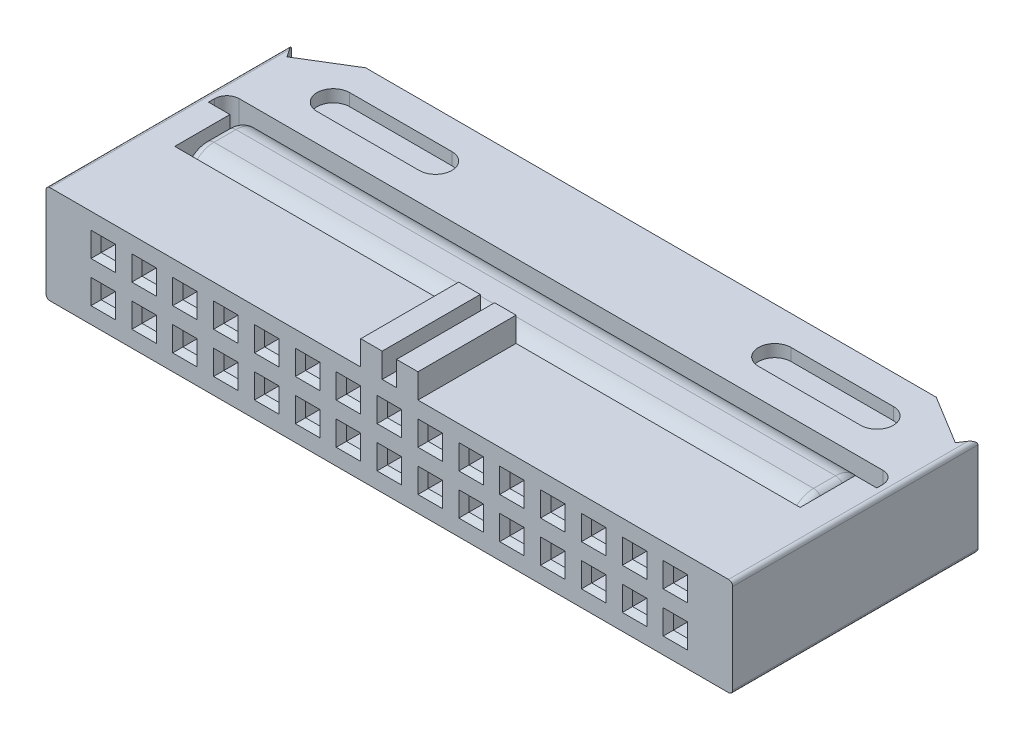
SolidWorks part; units mm, degrees
extrude "Base-Extrude" add sketch "Sketch1" against normal blind 16.256
sketch "Sketch1" plane through (0, 0, 0) normal (0, 0, 1) x (1, 0, 0)
  line L1 (-21.082, 3.048) -> (-1.778, 3.048)
  line L2 (-21.336, 2.794) -> (-21.336, -2.794)
  line L3 (-21.082, -3.048) -> (21.082, -3.048)
  line L4 (21.336, 2.794) -> (21.336, -2.794)
  line L5 (0, -6.7653) -> (0, 6.7653) construction
  line L6 (16.5234, 0) -> (-16.5234, 0) construction
  line L7 (1.778, 3.048) -> (21.082, 3.048)
  line L8 (-1.778, 4.572) -> (-0.4445, 4.572)
  line L9 (-1.778, 4.572) -> (-1.778, 3.048)
  line L10 (0.4445, 4.572) -> (1.778, 4.572)
  line L11 (1.778, 4.572) -> (1.778, 3.048)
  line L13 (-0.4445, 4.572) -> (-0.4445, 3.048)
  line L14 (-0.4445, 3.048) -> (0.4445, 3.048)
  line L15 (0.4445, 4.572) -> (0.4445, 3.048)
  arc A0 (-21.082, 3.048) -> (-21.336, 2.794) centre (-21.082, 2.794) ccw
  arc A1 (-21.336, -2.794) -> (-21.082, -3.048) centre (-21.082, -2.794) ccw
  arc A2 (21.336, -2.794) -> (21.082, -3.048) centre (21.082, -2.794) cw
  arc A3 (21.082, 3.048) -> (21.336, 2.794) centre (21.082, 2.794) cw
  point P4 (0, 3.048)
  point P7 (-21.336, 0)
  point P14 (0, 4.572)
  point P15 (0, 3.048)
  point P26 (21.336, -3.048)
  point P29 (21.336, 3.048)
  dimension "D8" = 0.254
  dimension "D9" = 0.254
  dimension "D1" = 42.672
  dimension "D2" = 6.096
  dimension "D3" = 3.556
  dimension "D4" = 1.524
  dimension "D5" = 0.889
  dimension "D6" = 1.778
  dimension "D7" = 21.336
ref_plane "Front" through (0, 0, 0) normal (0, 0, 1) x (1, 0, 0)
ref_plane "Top" through (0, 0, 0) normal (0, 1, 0) x (1, 0, 0)
ref_plane "Right" through (0, 0, 0) normal (1, 0, 0) x (0, 0, -1)
sketch "Sketch2" plane through (0, 3.048, 0) normal (0, 1, 0) x (-1, 0, 0)
  line L0 (-17.7294, -16.256) -> (-20.7645, -14.403)
  line L1 (-20.7645, -14.403) -> (-21.336, -15.2431)
  line L2 (21.336, -16.256) -> (21.336, -15.2431)
  line L3 (0, -17.4041) -> (0, 0.7826) construction
  line L4 (20.7645, -14.403) -> (21.336, -15.2431)
  line L5 (17.7294, -16.256) -> (20.7645, -14.403)
  line L6 (21.336, -16.256) -> (17.7294, -16.256)
  line L7 (-21.336, -16.256) -> (-21.336, -15.2431)
  line L8 (-21.336, -16.256) -> (-17.7294, -16.256)
  line L11 (-20.0025, -10.668) -> (20.0025, -10.668)
  line L12 (-20.7645, -9.525) -> (20.7645, -9.525)
  line L13 (-20.7645, -9.906) -> (-20.7645, -9.525)
  line L14 (20.7645, -9.906) -> (20.7645, -9.525)
  line L15 (0, 6.7653) -> (0, -6.7653) construction
  line L16 (-21.336, -16.256) -> (-21.336, 0) construction
  line L17 (-21.082, -16.256) -> (-1.778, -16.256) construction
  arc A0 (-20.7645, -9.906) -> (-20.0025, -10.668) centre (-20.0025, -9.906) ccw
  arc A1 (20.7645, -9.906) -> (20.0025, -10.668) centre (20.0025, -9.906) cw
  point P20 (0, -10.668)
  point P24 (0, -9.525)
  dimension "D1" = 0.762
  dimension "D2" = 40.005
  dimension "D3" = 5.588
  dimension "D4" = 1.143
  dimension "D5" = 3.556
  dimension "D6" = 1.016
  dimension "D7" = 1.853
extrude "Cut-Extrude1" cut sketch "Sketch2" against normal through all
sketch "Sketch3" plane through (-1.778, 0, 0) normal (-1, 0, 0) x (0, 0, 1)
  line L0 (0, -6.3682) -> (0, 6.3682) construction
  line L1 (-16.256, 4.572) -> (-6.096, 4.572)
  line L2 (-16.256, 4.572) -> (-16.256, 3.048)
  line L3 (-16.256, 3.048) -> (-6.096, 3.048)
  line L4 (-6.096, 4.572) -> (-6.096, 3.048)
  line L5 (-14.8697, 3.048) -> (0, 3.048) construction
  dimension "D1" = 6.096
extrude "Cut-Extrude2" cut sketch "Sketch3" against normal through all
sketch "Sketch4" plane through (0, 0, 0) normal (0, 0, 1) x (1, 0, 0)
  line L0 (-12.4713, 1.27) -> (21.336, 1.27) construction
  line L1 (-12.4713, -1.27) -> (21.336, -1.27) construction
  line L2 (17.78, 3.048) -> (17.78, -3.048) construction
  line L4 (21.336, -2.794) -> (21.336, 2.794) construction
  line L6 (21.336, 1.27) -> (21.336, -1.27) construction
  line L7 (16.5234, 0) -> (-16.5234, 0) construction
  line L8 (17.3355, -0.8255) -> (18.2245, -0.8255)
  line L9 (17.3355, -0.8255) -> (17.3355, -1.7145)
  line L10 (17.3355, -1.7145) -> (18.2245, -1.7145)
  line L11 (17.3355, 1.7145) -> (18.2245, 1.7145)
  line L12 (17.3355, 1.7145) -> (17.3355, 0.8255)
  line L13 (17.3355, 0.8255) -> (18.2245, 0.8255)
  line L14 (18.2245, 1.7145) -> (18.2245, 0.8255)
  line L15 (18.2245, -0.8255) -> (18.2245, -1.7145)
  point P11 (21.336, 0)
  point P16 (18.2245, -1.27)
  point P17 (17.3355, -1.27)
  point P23 (17.78, 1.7145)
  point P24 (18.2245, 1.27)
  point P25 (17.78, -1.7145)
  dimension "D1" = 3.556
  dimension "D2" = 0.889
  dimension "D3" = 2.54
  dimension "D4" = 0.889
  dimension "D6" = 0.889
  dimension "D7" = 0.889
extrude "Cut-Extrude3" cut sketch "Sketch4" against normal up to surface (6.096 mm away) up to face at (1.1113, 3.81, -6.096)
sketch "Sketch5" plane through (0, 0, 0) normal (0, 0, 1) x (1, 0, 0)
  line L1 (17.018, 2.032) -> (18.542, 2.032)
  line L2 (17.018, 2.032) -> (17.018, 0.508)
  line L3 (17.018, 0.508) -> (18.542, 0.508)
  line L4 (18.542, 2.032) -> (18.542, 0.508)
  line L5 (17.018, -0.508) -> (18.542, -0.508)
  line L6 (17.018, -0.508) -> (17.018, -2.032)
  line L7 (17.018, -2.032) -> (18.542, -2.032)
  line L8 (18.542, -0.508) -> (18.542, -2.032)
  line L11 (17.78, 2.032) -> (17.78, 0.508) construction
  line L12 (17.018, 1.27) -> (18.542, 1.27) construction
  line L14 (18.2245, 0.8255) -> (18.2245, 1.7145) construction
  line L15 (17.3355, 0.8255) -> (18.2245, 0.8255) construction
  line L16 (17.3355, -1.7145) -> (18.2245, -1.7145) construction
  line L17 (18.2245, -0.8255) -> (17.3355, -0.8255) construction
  point P10 (17.78, 2.032)
  point P17 (17.78, -1.7145)
  dimension "D1" = 0.3175
  dimension "D2" = 1.524
  dimension "D3" = 1.524
  dimension "D4" = 0.3175
  dimension "D5" = 0.3175
  dimension "D6" = 0.3175
extrude "Cut-Extrude4" cut sketch "Sketch5" against normal blind 0.762 draft 45
pattern_linear "LPattern1" count 15 spacing 2.54 along (-1, 0, 0) of "Cut-Extrude3", "Cut-Extrude4"
sketch "Sketch6" plane through (0, 0, 0) normal (1, 0, 0) x (0, 0, -1)
  line L0 (6.096, 3.048) -> (6.096, -3.048)
  line L1 (10.668, 3.048) -> (6.096, 3.048)
  line L2 (10.668, 3.048) -> (10.668, 1.778)
  line L3 (10.668, 1.778) -> (7.874, 1.778)
  line L4 (7.366, 1.27) -> (7.366, -3.048)
  line L5 (6.096, -3.048) -> (7.366, -3.048)
  line L6 (6.096, 4.572) -> (6.096, 3.048) construction
  arc A0 (7.874, 1.778) -> (7.366, 1.27) centre (7.874, 1.27) ccw
  dimension "D1" = 0.508
  dimension "D2" = 1.27
  dimension "D3" = 1.27
extrude "Cut-Extrude5" cut sketch "Sketch6" against normal mid plane 38.862
sketch "Sketch7" plane through (0, 0, -16.256) normal (0, 0, -1) x (-1, 0, 0)
  line L0 (-20.7645, -3.048) -> (-20.7645, 3.048) construction
  line L1 (-20.5105, -2.413) -> (20.5105, -2.413)
  line L2 (-20.7645, -2.667) -> (-20.7645, -3.048)
  line L3 (-20.7645, -3.048) -> (20.7645, -3.048)
  line L4 (20.7645, -2.667) -> (20.7645, -3.048)
  arc A0 (-20.5105, -2.413) -> (-20.7645, -2.667) centre (-20.5105, -2.667) ccw
  arc A1 (20.5105, -2.413) -> (20.7645, -2.667) centre (20.5105, -2.667) cw
  dimension "D1" = 0.254
  dimension "D2" = 0.635
extrude "Cut-Extrude6" cut sketch "Sketch7" against normal up to surface (6.731 mm away) up to face at (0, 1.2065, -9.525)
sketch "Sketch8" plane through (0, 3.048, 0) normal (0, 1, 0) x (-1, 0, 0)
  line L0 (-16.891, -14.4272) -> (-10.541, -14.4272)
  line L1 (-10.541, -12.3952) -> (-16.891, -12.3952)
  line L2 (-21.336, -15.2431) -> (-21.336, 0) construction
  line L3 (-17.7294, -16.256) -> (17.7294, -16.256) construction
  line L4 (0, -20.4815) -> (0, -9.8087) construction
  line L5 (10.541, -12.3952) -> (16.891, -12.3952)
  line L6 (16.891, -14.4272) -> (10.541, -14.4272)
  arc A0 (-10.541, -14.4272) -> (-10.541, -12.3952) centre (-10.541, -13.4112) ccw
  arc A1 (-16.891, -12.3952) -> (-16.891, -14.4272) centre (-16.891, -13.4112) ccw
  arc A2 (10.541, -14.4272) -> (10.541, -12.3952) centre (10.541, -13.4112) cw
  arc A3 (16.891, -12.3952) -> (16.891, -14.4272) centre (16.891, -13.4112) cw
  dimension "D1" = 1.016
  dimension "D2" = 6.35
  dimension "D3" = 4.445
  dimension "D4" = 2.8448
extrude "Cut-Extrude7" cut sketch "Sketch8" against normal blind 0.762
fillet "Fillet1" radius 0.254 1 edges at (0, 1.778, -9.525)
ref_plane "Plane1" through (0, 0, 0) normal (0, 1, 0) x (-1, 0, 0)
sketch "Sketch9" plane through (0, -3.048, 0) normal (0, -1, 0) x (1, 0, 0)
  line L0 (0, -9.525) -> (0, -10.668) construction
  line L1 (-20.7645, -9.525) -> (20.7645, -9.525) construction
  line L2 (-20.0025, -10.668) -> (20.0025, -10.668) construction
  point P6 (0, -10.0965)
other "CPoint1"
ref_axis "Axis1" through (0, -13.048, -10.0965) along (0, 1, 0)
sketch "Sketch10" plane through (0, -3.048, 0) normal (0, -1, 0) x (1, 0, 0)
  line L0 (-18.6292, -6.731) -> (18.6292, -6.731) construction
  line L1 (-18.6292, -6.1718) -> (18.6292, -6.1718)
  line L2 (-18.6292, -7.2902) -> (18.6292, -7.2902)
  arc A0 (-18.6292, -6.1718) -> (-18.6292, -7.2902) centre (-18.6292, -6.731) ccw
  arc A1 (18.6292, -7.2902) -> (18.6292, -6.1718) centre (18.6292, -6.731) ccw
  point P2 (0, -6.731)
sketch "Sketch11" plane through (0, 0, 0) normal (1, 0, 0) x (0, 0, -1)
  line L0 (6.731, -3.048) -> (6.731, 1.2952)
  line L1 (7.731, 2.2952) -> (9.0965, 2.2952)
  line L2 (10.0965, 1.2952) -> (10.0965, -3.048)
  arc A0 (6.731, 1.2952) -> (7.731, 2.2952) centre (7.731, 1.2952) cw
  arc A1 (9.0965, 2.2952) -> (10.0965, 1.2952) centre (9.0965, 1.2952) cw
  dimension "D1" = 1
sweep "Sweep1" add profiles "Sketch10" path "Sketch11"
